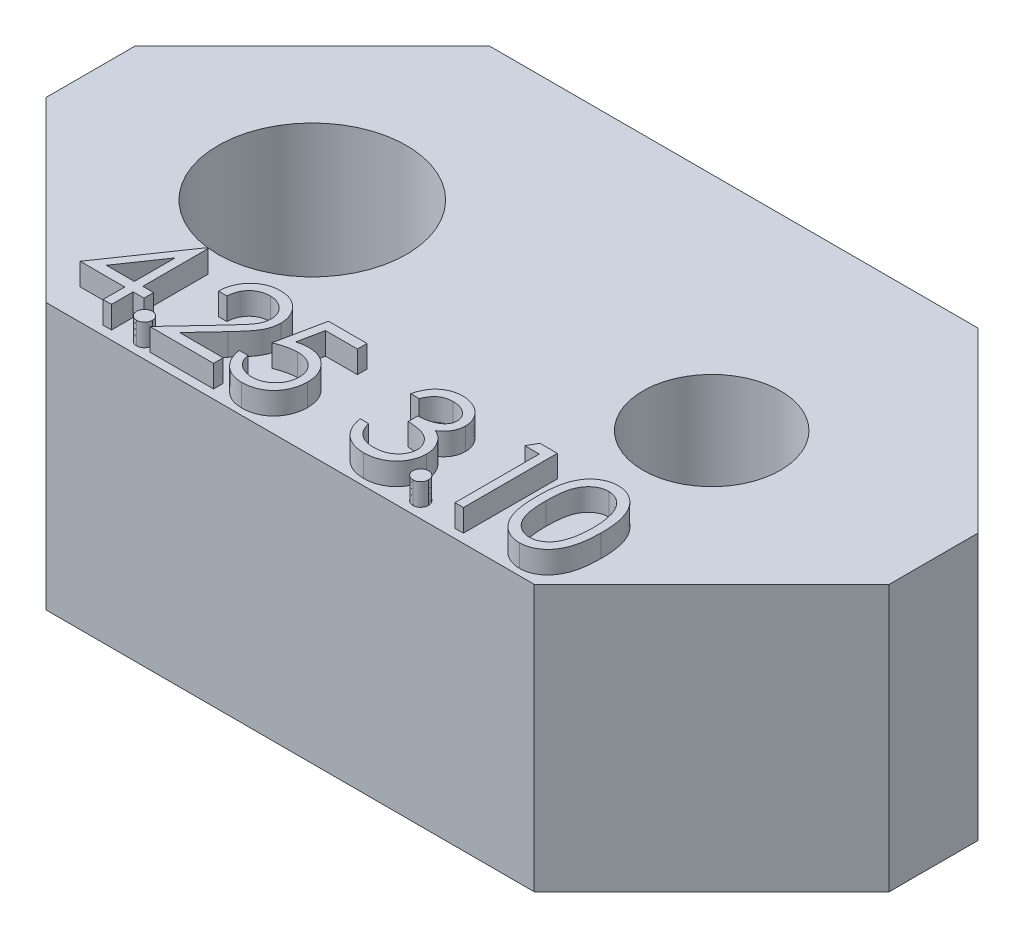
SolidWorks part; units mm, degrees
ref_plane "Спереди" through (0, 0, 0) normal (0, 0, 1) x (1, 0, 0)
ref_plane "Сверху" through (0, 0, 0) normal (0, 1, 0) x (1, 0, 0)
ref_plane "Справа" through (0, 0, 0) normal (1, 0, 0) x (0, 0, -1)
sketch "Эскиз1" plane through (0, 0, 0) normal (0, 1, 0) x (1, 0, 0)
  line L0 (-9.5, 0) -> (9.5, 0) construction
  line L1 (5.5, 5) -> (-5.5, 5)
  line L2 (9.5, 1) -> (9.5, -1)
  line L3 (5.5, -5) -> (-5.5, -5)
  line L4 (-9.5, 1) -> (-9.5, -1)
  line L5 (9.5, 5) -> (-9.5, -5) construction
  line L6 (9.5, -5) -> (-9.5, 5) construction
  line L7 (-5.5, 5) -> (-9.5, 1)
  line L8 (-9.5, -1) -> (-5.5, -5)
  line L9 (9.5, -1) -> (5.5, -5)
  line L10 (5.5, 5) -> (9.5, 1)
  circle A0 centre (-4.5, 0) radius 2.125
  circle A1 centre (4.5, 0) radius 1.55
  point P0 (0, 0)
  dimension "D1" = 4.25
  dimension "D2" = 3.1
  dimension "D3" = 5
  dimension "D4" = 9
  dimension "D5" = 5
  dimension "D6" = 10
  dimension "D7" = 19
extrude "Бобышка-Вытянуть1" add sketch "Эскиз1" along normal blind 6 contours L10 L1 L7 L4 L8 L3 L9 L2 A1 A0 region at (0.2192, 0, 0)
extrude "Бобышка-Вытянуть2" add sketch "Эскиз1<3>" along normal blind 2 contours A0 | A1 region at (-4.5, 0, 0) region at (4.5, 0, 0)
sketch "Эскиз1<3>" plane through (0, 0, 0) normal (0, 1, 0) x (1, 0, 0) same geometry as "Эскиз1"
sketch "Эскиз3" plane through (0, 6, 0) normal (0, 1, 0) x (1, 0, 0)
  line L0 (-5.5, -5) -> (-5.5, -4.8) construction
  line L1 (-5.5, -4.8) -> (5.5, -4.8) construction
  text T0 "4.25  3.10" font "Century Gothic" height in points 8
  dimension "D1" = 0.2
  dimension "D2" = 11
extrude "Бобышка-Вытянуть3" add sketch "Эскиз3" along normal blind 0.5
